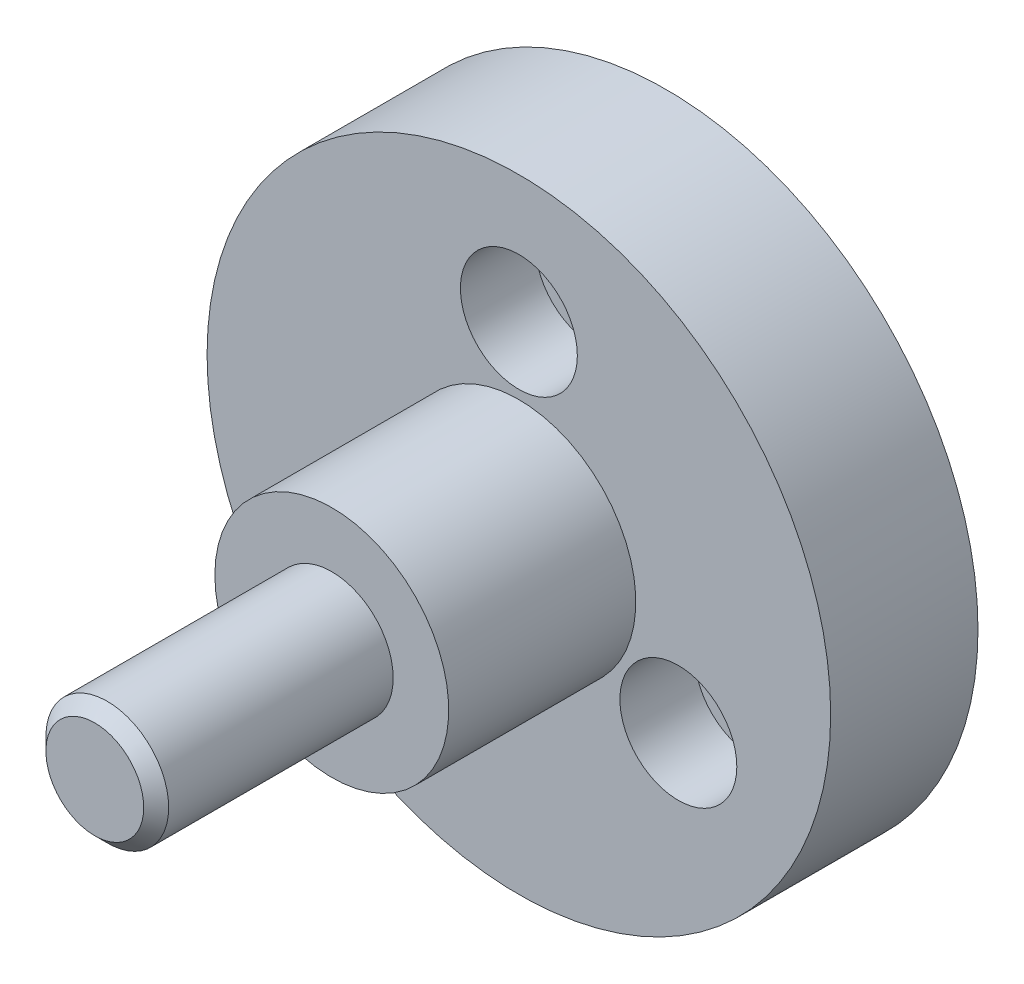
SolidWorks part; units mm, degrees
material "6061 Alloy"
ref_plane "Front Plane" through (0, 0, 0) normal (0, 0, 1) x (1, 0, 0)
ref_plane "Top Plane" through (0, 0, 0) normal (0, 1, 0) x (1, 0, 0)
ref_plane "Right Plane" through (0, 0, 0) normal (1, 0, 0) x (0, 0, -1)
sketch "Sketch1" plane through (0, 0, 0) normal (0, 0, 1) x (1, 0, 0)
  circle A0 centre (0, 0) radius 12.7
  dimension "D2" = 25.4
extrude "Mounting Flange" add sketch "Sketch1" along normal blind 6
sketch "Sketch2" plane through (0, 0, 6) normal (0, 0, 1) x (1, 0, 0)
  circle A0 centre (0, 0) radius 2.5
  dimension "D1" = 5
sketch "Sketch3" plane through (0, 0, 0) normal (0, 0, -1) x (-1, 0, 0)
  circle A0 centre (0, 0) radius 6.35
  dimension "D1" = 12.7
extrude "Motor Shaft Relief" cut sketch "Sketch3" against normal blind 2.54
extrude "Drive Shaft" add sketch "Sketch2" along normal blind 17.272 contours A0
chamfer "Chamfer1" distance 0.508 angle 45 1 edges at (2.5, 0, 23.272)
sketch "Sketch5" plane through (0, 0, 6) normal (0, 0, 1) x (1, 0, 0)
  circle A0 centre (0, 0) radius 4.7625
  dimension "D1" = 9.525
extrude "Shaft Support Shoulder" add sketch "Sketch5" along normal blind 7.62
hole_wizard "M2.5 Clearance Hole" positions "Sketch7" profile "Sketch6" hole size "M2.5" standard "ANSI Metric" end condition up to next
sketch "Sketch7" plane through (0, 0, 6) normal (0, 0, 1) x (1, 0, 0)
  circle A0 centre (0, 0) radius 7.5 construction
  point P0 (0, 7.5)
  dimension "D1" = 15
sketch "Sketch6" plane through (0, 7.5, 6) normal (1, 0, 0) x (0, -1, 0)
  line L0 (0, 0) -> (0, 6.001)
  line L1 (0, 6.001) -> (1.45, 6.001)
  line L2 (1.45, 6.001) -> (1.45, 0)
  line L5 (1.45, 0) -> (0, 0)
  line L11 (0, -6.35) -> (0, 107.95) construction
  dimension "Thru Hole Dia." = 2.9
  dimension "Thru Hole Depth" = 6.001
sketch "Sketch8" plane through (0, 0, 6) normal (0, 0, 1) x (1, 0, 0)
  circle A0 centre (0, 7.5) radius 2.3813
  dimension "D1" = 4.7625
extrude "M2.5 Tight Couterbore" cut sketch "Sketch8" against normal blind 3.048 contours A0
ref_axis "Axis1" through (0, 0, -1.1636) along (0, 0, 1)
pattern_circular "CirPattern" count 3 over 360 about axis through (0, 0, -1.1636) along (0, 0, 1) of "M2.5 Clearance Hole", "M2.5 Tight Couterbore"
